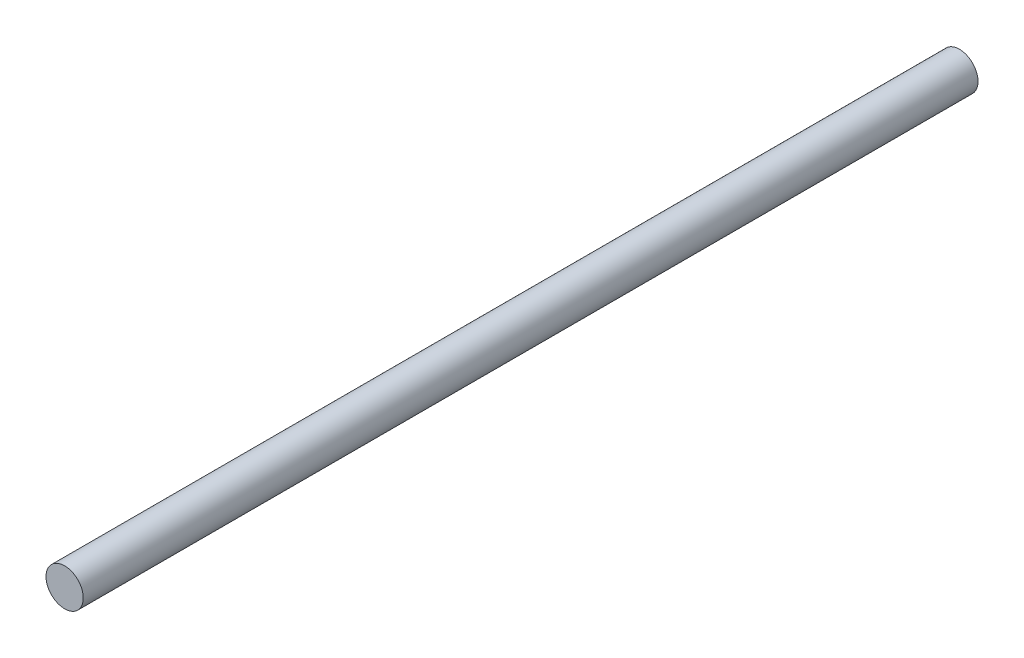
SolidWorks part; units mm, degrees
ref_plane "Front Plane" through (0, 0, 0) normal (0, 0, 1) x (1, 0, 0)
ref_plane "Top Plane" through (0, 0, 0) normal (0, 1, 0) x (1, 0, 0)
ref_plane "Right Plane" through (0, 0, 0) normal (1, 0, 0) x (0, 0, -1)
sketch "Sketch1" plane through (0, 0, 0) normal (0, 0, 1) x (1, 0, 0)
  circle A0 centre (0, 0) radius 3.175
  dimension "D1" = 6.35
extrude "Boss-Extrude1" add sketch "Sketch1" along normal blind 152.4
